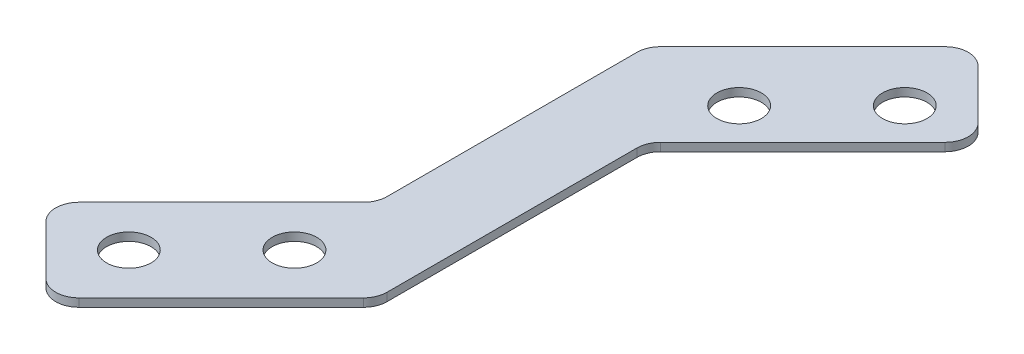
SolidWorks part; units mm, degrees
material "1060 Alloy"
ref_plane "Front Plane" through (0, 0, 0) normal (0, 0, 1) x (1, 0, 0)
ref_plane "Top Plane" through (0, 0, 0) normal (0, 1, 0) x (1, 0, 0)
ref_plane "Right Plane" through (0, 0, 0) normal (1, 0, 0) x (0, 0, -1)
sketch "Sketch1" plane through (0, 0, 0) normal (0, 1, 0) x (1, 0, 0)
  line L8 (0, 0) -> (0, 23)
  line L9 (0, 23) -> (14.1421, 37.1421)
  line L10 (14.1421, 37.1421) -> (7.0711, 44.2132)
  line L11 (7.0711, 44.2132) -> (-7.0711, 30.0711)
  line L12 (-7.0711, 30.0711) -> (-7.0711, 7.0711)
  line L13 (-7.0711, 7.0711) -> (-21.2132, -7.0711)
  line L15 (-14.1421, -14.1421) -> (0, 0)
  line L16 (-14.1421, -14.1421) -> (-21.2132, -7.0711)
  line L17 (-7.0711, 30.0711) -> (0, 23) construction
  dimension "D1" = 23
  dimension "D2" = 135
  dimension "D3" = 135
  dimension "D4" = 10
  dimension "D5" = 10
  dimension "D6" = 20
  dimension "D7" = 20
base flange "Base-Flange2" sketch "Sketch1" thickness 0.7 reverse thickness direction no parameters "D1"=1
hole_wizard "#6 Clearance Hole1" positions "Sketch10" profile "Sketch11" hole size "#6" standard "ANSI Inch" end condition through all
sketch "Sketch10" plane through (0, 0, 0) normal (0, 1, 0) x (1, 0, 0)
  line L0 (-14.1398, -7.0734) -> (-7.0688, -0.0023) construction
  line L2 (1.2374, 29.6539) -> (8.3085, 36.7249) construction
  line L4 (-14.1421, -14.1421) -> (0, 0) construction
  line L5 (0, 23) -> (14.1421, 37.1421) construction
  line L6 (-21.2132, -7.0711) -> (-14.1421, -14.1421) construction
  point P0 (-14.1398, -7.0734)
  point P2 (-7.0688, -0.0023)
  point P13 (1.2374, 29.6539)
  point P14 (8.3085, 36.7249)
  dimension "D1" = 5
  dimension "D2" = 10
  dimension "D4" = 10
  dimension "D5" = 4.9967
  dimension "D6" = 3.83
sketch "Sketch11" plane through (-14.1398, 0, 7.0734) normal (1, 0, 0) x (0, 0, 1)
  line L0 (0, 0) -> (0, 0.7)
  line L1 (0, 0.7) -> (1.8986, 0.7)
  line L2 (1.8986, 0.7) -> (1.8986, 0)
  line L5 (1.8986, 0) -> (0, 0)
  line L11 (0, -6.35) -> (0, 107.95) construction
  dimension "Thru Hole Dia." = 3.7973
  dimension "Thru Hole Depth" = 0.7
fillet "Fillet1" radius 2 8 edges at (7.0711, -0.35, -44.2132) (14.1421, -0.35, -37.1421) (-7.0711, -0.35, -7.0711) (0, -0.35, -23) (-7.0711, -0.35, -30.0711) (0, -0.35, 0) (-21.2132, -0.35, 7.0711) (-14.1421, -0.35, 14.1421)
sketch "Bend-Lines3" [suppressed] plane through (0, 0, 0) normal (0, 1, 0) x (1, 0, 0)
sketch "Bounding-Box3" [suppressed] plane through (0, 0, 0) normal (0, 1, 0) x (1, 0, 0)
sheet metal parameters "Sheet-Metal2" thickness 0.7 parameters "D1"=1
flat pattern "Flat-Pattern2" [suppressed]
sketch "Bend-Lines4" plane through (0, 0, 0) normal (0, 1, 0) x (1, 0, 0)
sketch3d "Bounding-Box4" [suppressed]
  line L0 (18.9739, 32.9272, 0) -> (-12.0539, -20.9183, 0) construction
  line L1 (4.9829, 40.9894, 0) -> (-26.045, -12.8561, 0) construction
  line L2 (18.9739, 32.9272, 0) -> (4.9829, 40.9894, 0) construction
  line L3 (-12.0539, -20.9183, 0) -> (-26.045, -12.8561, 0) construction
sheet metal parameters "Sheet-Metal3" thickness 0.7 parameters "D1"=1
flat pattern "Flat-Pattern2"
sketch "Bend-Lines4" plane through (0, 0, 0) normal (0, 1, 0) x (1, 0, 0)
sketch3d "Bounding-Box4" [suppressed]
  line L0 (14.7481, 40.7001, 0) -> (-6.1738, -16.3651, 0) construction
  line L1 (-0.8973, 46.4361, 0) -> (-21.8191, -10.629, 0) construction
  line L2 (14.7481, 40.7001, 0) -> (-0.8973, 46.4361, 0) construction
  line L3 (-6.1738, -16.3651, 0) -> (-21.8191, -10.629, 0) construction
equation "\"D2@Sketch1\"=90+45"
equation "\"D3@Sketch1\"=\"D2@Sketch1\""
equation "\"D5@Sketch1\"=\"D4@Sketch1\""
equation "\"D7@Sketch1\"=\"D6@Sketch1\""
